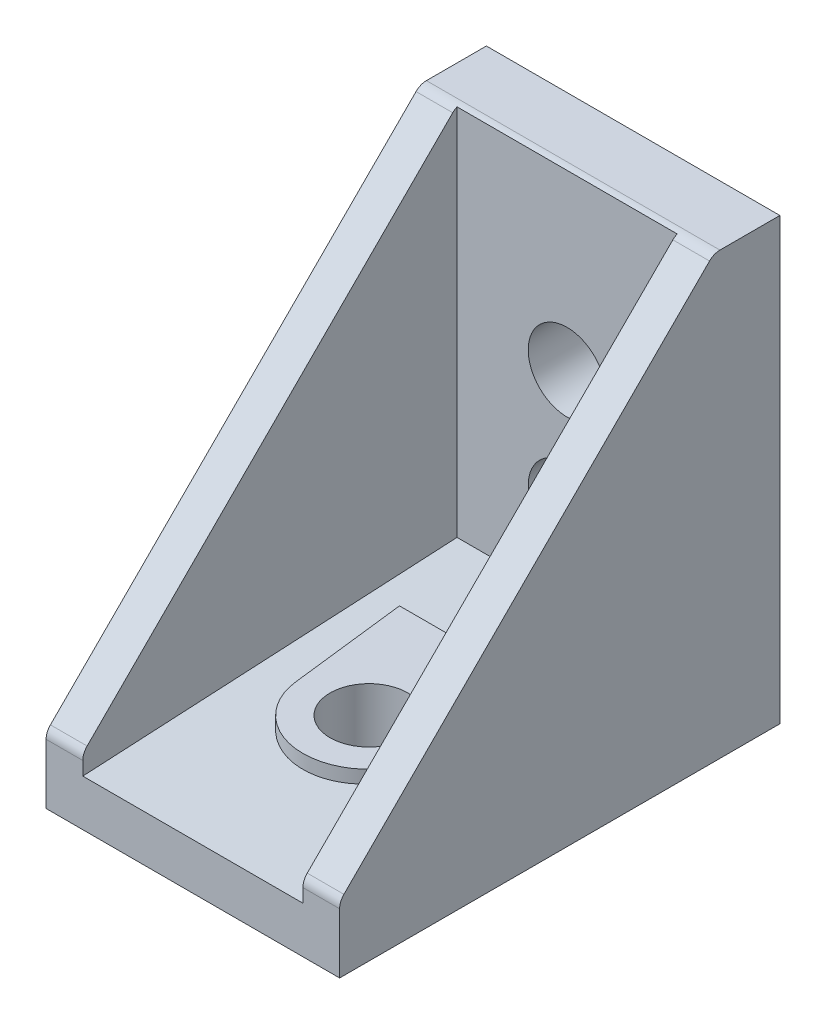
SolidWorks part; units mm, degrees
ref_plane "Front Plane" through (0, 0, 0) normal (0, 0, 1) x (1, 0, 0)
ref_plane "Top Plane" through (0, 0, 0) normal (0, 1, 0) x (1, 0, 0)
ref_plane "Right Plane" through (0, 0, 0) normal (1, 0, 0) x (0, 0, -1)
ref_plane "Plane1" through (0, 0, 0) normal (1, 0, 0) x (0, 0, -1)
sketch "Sketch1" plane through (0, 0, 0) normal (1, 0, 0) x (0, 0, -1)
  line L0 (-30, 4.0858) -> (-30, 0)
  line L1 (-30, 0) -> (0, 0)
  line L2 (0, 0) -> (0, 30)
  line L3 (0, 30) -> (-4.0858, 30)
  line L4 (-4.7929, 29.7071) -> (-29.7071, 4.7929)
  arc A0 (-4.0858, 30) -> (-4.7929, 29.7071) centre (-4.0858, 29) ccw
  arc A1 (-29.7071, 4.7929) -> (-30, 4.0858) centre (-29, 4.0858) ccw
extrude "Boss-Extrude1" add sketch "Sketch1" against normal blind 10 and the other way blind 10
ref_plane "Plane2" through (0, 0, 0) normal (1, 0, 0) x (0, 0, -1)
sketch "Sketch2" plane through (0, 0, 0) normal (1, 0, 0) x (0, 0, -1)
  line L0 (-34.5, 34.5) -> (-34.5, 2.9278)
  line L1 (-34.5, 2.9278) -> (-4.5, 4.5)
  line L2 (-4.5, 4.5) -> (-4.5, 34.5)
  line L3 (-4.5, 34.5) -> (-34.5, 34.5)
extrude "Cut-Extrude1" cut sketch "Sketch2" against normal blind 7.5 and the other way blind 7.5
ref_plane "Plane3" through (0, 4.5, 0) normal (0, 1, 0) x (1, 0, 0)
sketch "Sketch3" plane through (0, 4.5, 0) normal (0, 1, 0) x (1, 0, 0)
  line L0 (-5.4209, -10.5) -> (-4.4687, -18.5299)
  line L1 (4.4687, -18.5299) -> (5.4209, -10.5)
  line L2 (5.4209, -10.5) -> (-5.4209, -10.5)
  arc A0 (-4.4687, -18.5299) -> (4.4687, -18.5299) centre (0, -18) ccw
extrude "Boss-Extrude2" add sketch "Sketch3" against normal blind 2.25
ref_plane "Plane4" through (0, 0, 0) normal (0, 0, 1) x (1, 0, 0)
sketch "Sketch4" plane through (0, 0, 0) normal (0, 0, 1) x (1, 0, 0)
  circle A0 centre (0, 18) radius 2.65
extrude "Cut-Extrude2" cut sketch "Sketch4" along normal blind 4.5
ref_plane "Plane5" through (0, 0, 0) normal (0, 0, 1) x (1, 0, 0)
sketch "Sketch5" plane through (0, 0, 0) normal (0, 0, 1) x (1, 0, 0)
  circle A0 centre (0, 10) radius 2.65
extrude "Cut-Extrude3" cut sketch "Sketch5" along normal blind 4.5
ref_plane "Plane6" through (0, 0, 0) normal (0, 1, 0) x (1, 0, 0)
sketch "Sketch6" plane through (0, 0, 0) normal (0, 1, 0) x (1, 0, 0)
  circle A0 centre (0, -18) radius 2.65
extrude "Cut-Extrude4" cut sketch "Sketch6" along normal blind 4.5
ref_plane "Plane7" through (0, 0, 0) normal (0, 1, 0) x (1, 0, 0)
sketch "Sketch7" plane through (0, 0, 0) normal (0, 1, 0) x (1, 0, 0)
  line L0 (-10, -30) -> (10, -30)
  line L1 (10, -30) -> (10, 0)
  line L2 (10, 0) -> (-10, 0)
  line L3 (-10, 0) -> (-10, -30)
extrude "Boss-Extrude3" add sketch "Sketch7" against normal blind 1
ref_plane "Plane8" through (0, 0, 0) normal (0, 1, 0) x (1, 0, 0)
sketch "Sketch8" plane through (0, 0, 0) normal (0, 1, 0) x (1, 0, 0)
  line L0 (-10, -30) -> (10, -30)
  line L1 (10, -30) -> (10, 0)
  line L2 (10, 0) -> (-10, 0)
  line L3 (-10, 0) -> (-10, -30)
  line L4 (-3, -24.3) -> (-3, -26.7)
  line L5 (-2.7, -27) -> (2.7, -27)
  line L6 (3, -26.7) -> (3, -24.3)
  line L7 (2.7, -24) -> (-2.7, -24)
  line L8 (-3, -5.3) -> (-3, -10.7)
  line L9 (-2.7, -11) -> (2.7, -11)
  line L10 (3, -10.7) -> (3, -5.3)
  line L11 (2.7, -5) -> (-2.7, -5)
  arc A0 (-3, -26.7) -> (-2.7, -27) centre (-2.7, -26.7) ccw
  arc A1 (2.7, -27) -> (3, -26.7) centre (2.7, -26.7) ccw
  arc A2 (3, -24.3) -> (2.7, -24) centre (2.7, -24.3) ccw
  arc A3 (-2.7, -24) -> (-3, -24.3) centre (-2.7, -24.3) ccw
  arc A4 (-3, -10.7) -> (-2.7, -11) centre (-2.7, -10.7) ccw
  arc A5 (2.7, -11) -> (3, -10.7) centre (2.7, -10.7) ccw
  arc A6 (3, -5.3) -> (2.7, -5) centre (2.7, -5.3) ccw
  arc A7 (-2.7, -5) -> (-3, -5.3) centre (-2.7, -5.3) ccw
extrude "Cut-Extrude5" cut sketch "Sketch8" against normal blind 1
ref_plane "Plane9" through (0, 0, 0) normal (0, 0, 1) x (1, 0, 0)
sketch "Sketch9" plane through (0, 0, 0) normal (0, 0, 1) x (1, 0, 0)
  line L0 (-10, 30) -> (-10, 0)
  line L1 (-10, 0) -> (10, 0)
  line L2 (10, 0) -> (10, 30)
  line L3 (10, 30) -> (-10, 30)
extrude "Boss-Extrude4" add sketch "Sketch9" against normal blind 1
ref_plane "Plane10" through (0, 0, 0) normal (0, 0, 1) x (1, 0, 0)
sketch "Sketch10" plane through (0, 0, 0) normal (0, 0, 1) x (1, 0, 0)
  line L0 (-10, 30) -> (-10, 0)
  line L1 (-10, 0) -> (10, 0)
  line L2 (10, 0) -> (10, 30)
  line L3 (10, 30) -> (-10, 30)
  line L4 (2.6024, 10.5) -> (3, 10.5)
  line L5 (3, 10.5) -> (3, 12)
  line L6 (2, 13) -> (0.5, 13)
  line L7 (0.5, 13) -> (0.5, 12.6024)
  line L8 (0.5, 7.3976) -> (0.5, 7)
  line L9 (0.5, 7) -> (2, 7)
  line L10 (3, 8) -> (3, 9.5)
  line L11 (3, 9.5) -> (2.6024, 9.5)
  line L12 (-3, 12) -> (-3, 10.5)
  line L13 (-3, 10.5) -> (-2.6024, 10.5)
  line L14 (-0.5, 12.6024) -> (-0.5, 13)
  line L15 (-0.5, 13) -> (-2, 13)
  line L16 (-3, 9.5) -> (-3, 8)
  line L17 (-2, 7) -> (-0.5, 7)
  line L18 (-0.5, 7) -> (-0.5, 7.3976)
  line L19 (-2.6024, 9.5) -> (-3, 9.5)
  arc A0 (0.5, 12.6024) -> (2.6024, 10.5) centre (0, 10) cw
  arc A1 (3, 12) -> (2, 13) centre (2, 12) ccw
  arc A2 (2, 7) -> (3, 8) centre (2, 8) ccw
  arc A3 (2.6024, 9.5) -> (0.5, 7.3976) centre (0, 10) cw
  arc A4 (-2.6024, 10.5) -> (-0.5, 12.6024) centre (0, 10) cw
  arc A5 (-2, 13) -> (-3, 12) centre (-2, 12) ccw
  arc A6 (-3, 8) -> (-2, 7) centre (-2, 8) ccw
  arc A7 (-0.5, 7.3976) -> (-2.6024, 9.5) centre (0, 10) cw
extrude "Cut-Extrude6" cut sketch "Sketch10" against normal blind 1
